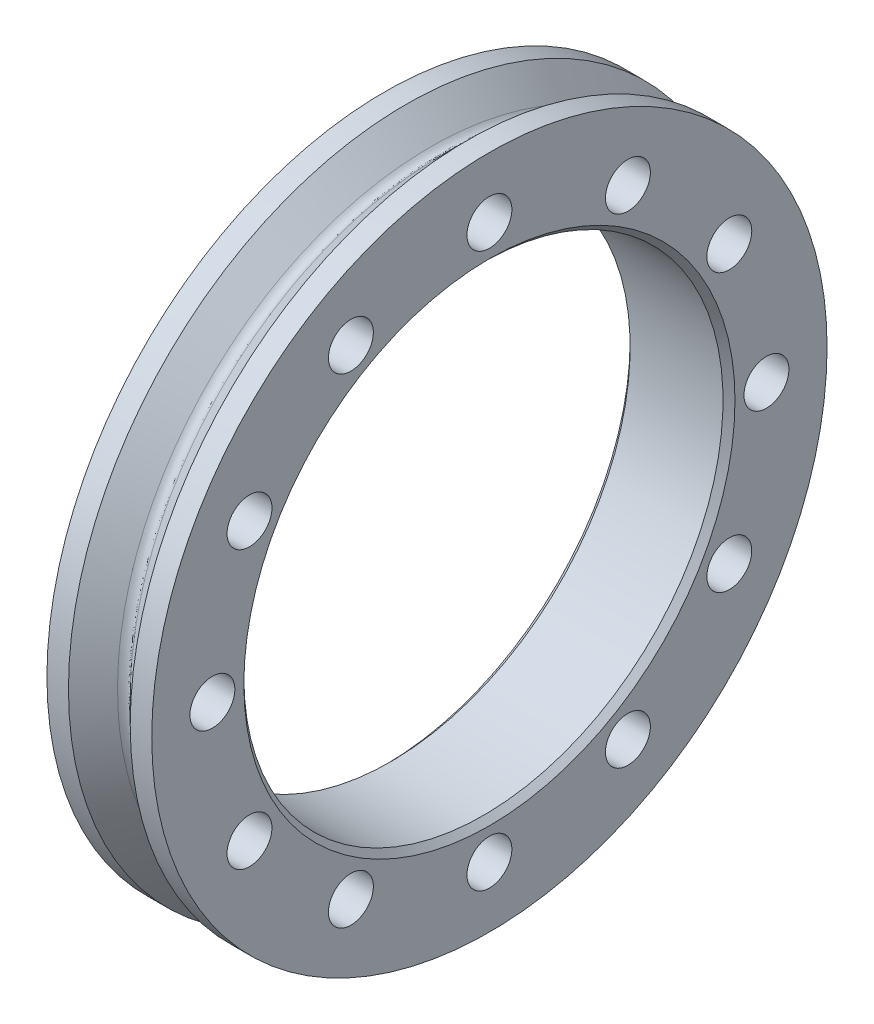
SolidWorks part; units mm, degrees
ref_plane "Front Plane" through (0, 0, 0) normal (0, 0, 1) x (1, 0, 0)
ref_plane "Top Plane" through (0, 0, 0) normal (0, 1, 0) x (1, 0, 0)
ref_plane "Right Plane" through (0, 0, 0) normal (1, 0, 0) x (0, 0, -1)
sketch "Sketch1" plane through (0, 0, 0) normal (0, 0, 1) x (1, 0, 0)
  line L0 (0, 0) -> (-70, 0) construction
  line L1 (17.5, 112.75) -> (-17.5, 112.75)
  line L2 (17.5, 112.75) -> (17.5, 80)
  line L3 (17.5, 80) -> (-17.5, 80)
  line L4 (-17.5, 112.75) -> (-17.5, 80)
  line L5 (17.5, 112.75) -> (-17.5, 80) construction
  line L6 (17.5, 80) -> (-17.5, 112.75) construction
  line L7 (0, 96.375) -> (0, 132.5854) construction
  line L8 (0, 125.0637) -> (11.3137, 113.75)
  line L9 (0, 125.0637) -> (-11.3137, 113.75)
  line L10 (11.3137, 113.75) -> (0, 102.4363)
  line L11 (-11.3137, 113.75) -> (0, 102.4363)
  line L12 (0, 125.0637) -> (0, 102.4363) construction
  line L13 (11.3137, 113.75) -> (-11.3137, 113.75) construction
  circle A0 centre (0, 113.75) radius 8 construction
  point P0 (0, 96.375)
  point P11 (0, 113.75)
  dimension "D5" = 16
  dimension "D1" = 80
  dimension "D2" = 112.75
  dimension "D3" = 35
  dimension "D4" = 113.75
revolve "Revolve1" add sketch "Sketch1" angle 360 about L0 region at (0, 95.0516, 0)
chamfer "Chamfer1" distance 2 angle 45 2 edges at (-17.5, 0, -80) (17.5, 0, -80)
fillet "Fillet1" radius 3 1 edges at (0, 0, -102.4363) curvature continuous yes
ref_axis "Axis1" through (-15.5, 0, 0) along (1, 0, 0)
sketch "Sketch3" plane through (17.5, 0, 0) normal (1, 0, 0) x (0, 0, -1)
  line L0 (0, -92.5) -> (0, 0) construction
  circle A0 centre (0, 0) radius 92.5 construction
  dimension "D1" = 185
hole_wizard "CBORE for M10 Hex Head Bolt1" positions "3DSketch1" profile "Sketch4" counterbore size "M10" standard "ISO" end condition through all
sketch3d "3DSketch1"
  point P0 (17.5, -92.5, 0)
sketch "Sketch4" plane through (17.5, -92.5, 0) normal (0, 1, 0) x (0, 0, -1)
  line L0 (0, 0) -> (0, 35)
  line L1 (0, 35) -> (5.25, 35)
  line L3 (5.25, 35) -> (5.25, 10.8)
  line L4 (5.25, 10.8) -> (7.5, 10.8)
  line L5 (7.5, 10.8) -> (7.5, 0)
  line L7 (7.5, 0) -> (0, 0)
  line L11 (0, -6.35) -> (0, 107.95) construction
  dimension "Thru Hole Dia." = 10.5
  dimension "Thru Hole Depth" = 35
  dimension "C'Bore Dia." = 15
  dimension "C'Bore Depth" = 10.8
pattern_circular "CirPattern1" count 12 over 360 about axis through (-15.5, 0, 0) along (1, 0, 0) of "CBORE for M10 Hex Head Bolt1"
